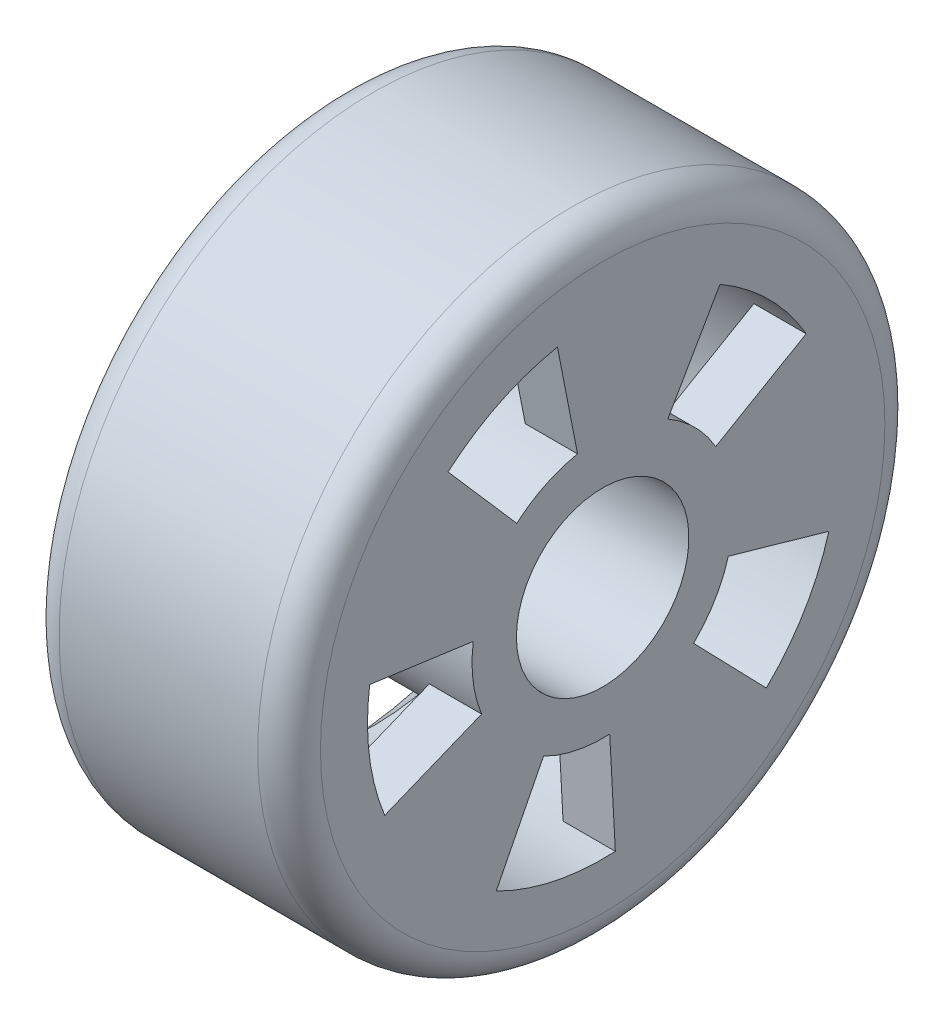
SolidWorks part; units mm, degrees
ref_plane "Front Plane" through (0, 0, 0) normal (0, 0, 1) x (1, 0, 0)
ref_plane "Top Plane" through (0, 0, 0) normal (0, 1, 0) x (1, 0, 0)
ref_plane "Right Plane" through (0, 0, 0) normal (1, 0, 0) x (0, 0, -1)
sketch "Sketch1" plane through (0, 0, 0) normal (1, 0, 0) x (0, 0, -1)
  circle A0 centre (0, 0) radius 30
  dimension "D1" = 60
extrude "Boss-Extrude1" add sketch "Sketch1" along normal blind 25
fillet "Fillet1" radius 3 2 edges at (0, 0, -30) (25, 0, -30)
sketch "Sketch3" plane through (0, 0, 0) normal (-1, 0, 0) x (0, 0, 1)
  circle A0 centre (0, 0) radius 22.5
  dimension "D1" = 45
extrude "Cut-Extrude1" cut sketch "Sketch3" against normal blind 20
chamfer "Chamfer1" distance 3 angle 45 1 edges at (0, 0, 22.5)
sketch "Sketch2" plane through (25, 0, 0) normal (-1, 0, 0) x (0, 0, 1)
  line L0 (-6.2332, 10.835) -> (-11.2197, 19.503)
  line L1 (-10.8156, 6.2668) -> (-19.4681, 11.2803)
  line L2 (-10.8156, 6.2668) -> (0, 0) construction
  line L3 (0, 0) -> (-6.2332, 10.835) construction
  arc A0 (-6.2332, 10.835) -> (-10.8156, 6.2668) centre (0, 0) ccw
  arc A1 (-11.2197, 19.503) -> (-19.4681, 11.2803) centre (0, 0) ccw
  dimension "D1" = 25
  dimension "D2" = 45
  dimension "D3" = 30
extrude "Cut-Extrude2" cut sketch "Sketch2" along normal through all
pattern_circular "CirPattern1" count 5 every 71 about axis through (25, 0, 0) along (1, 0, 0) of "Cut-Extrude2"
sketch "Sketch4" plane through (20, 0, 0) normal (-1, 0, 0) x (0, 0, 1)
  circle A0 centre (0, 0) radius 12.5
  dimension "D1" = 25
extrude "Boss-Extrude2" add sketch "Sketch4" along normal blind 15
sketch "Sketch5" plane through (5, 0, 0) normal (-1, 0, 0) x (0, 0, 1)
  circle A0 centre (0, 0) radius 8.25
  dimension "D1" = 16.5
extrude "Cut-Extrude3" cut sketch "Sketch5" against normal through all
sketch "Sketch6" plane through (5, 0, 0) normal (-1, 0, 0) x (0, 0, 1)
  circle A0 centre (0, 0) radius 10
  circle A1 centre (0, 0) radius 5
  dimension "D1" = 20
extrude "Boss-Extrude3" add sketch "Sketch6" against normal blind 3
